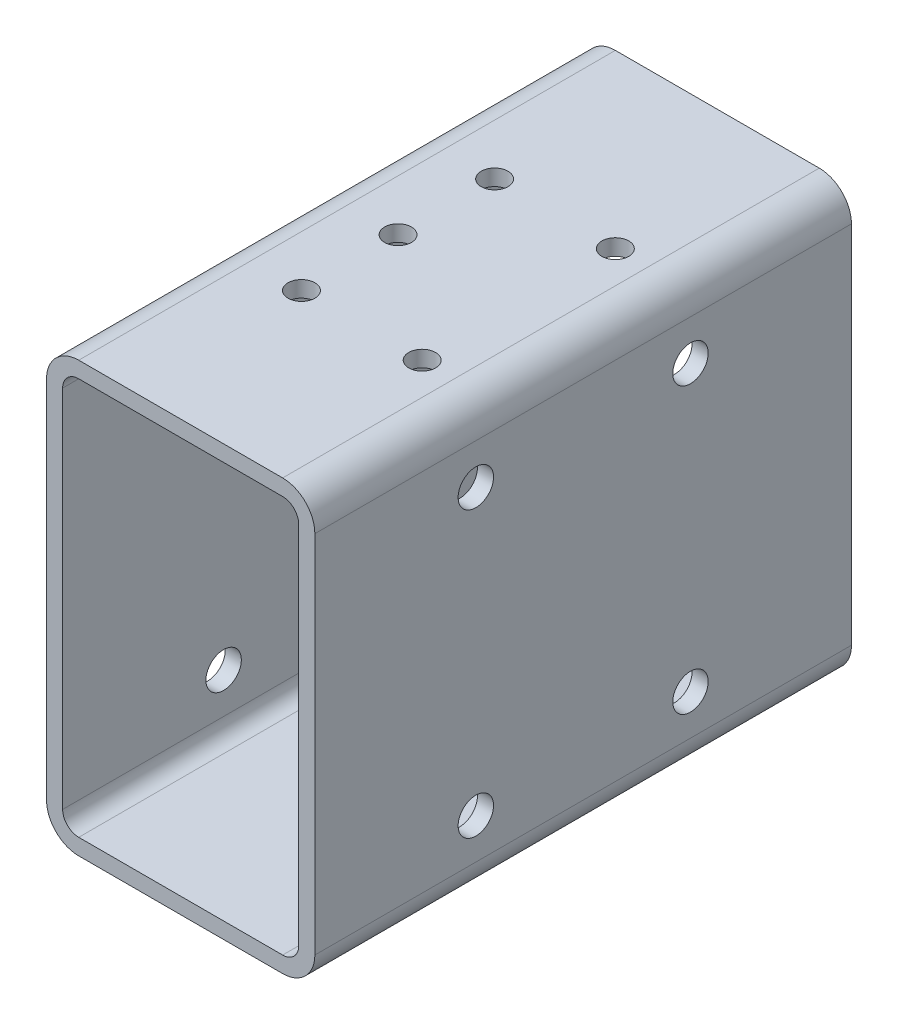
SolidWorks part; units mm, degrees
ref_plane "Front Plane" through (0, 0, 0) normal (0, 0, 1) x (1, 0, 0)
ref_plane "Top Plane" through (0, 0, 0) normal (0, 1, 0) x (1, 0, 0)
ref_plane "Right Plane" through (0, 0, 0) normal (1, 0, 0) x (0, 0, -1)
sketch "Sketch1" plane through (0, 0, 0) normal (0, 0, 1) x (1, 0, 0)
  line L0 (19, 37) -> (-19, 37)
  line L1 (19, -40) -> (-19, -40)
  line L2 (25, -34) -> (25, 34)
  line L3 (19, 40) -> (-19, 40)
  line L4 (-25, -34) -> (-25, 34)
  line L5 (25, -40) -> (-25, 40) construction
  line L6 (25, 40) -> (-25, -40) construction
  line L7 (-22, -34) -> (-22, 34)
  line L8 (19, -37) -> (-19, -37)
  line L9 (22, -34) -> (22, 34)
  arc A0 (-19, -40) -> (-25, -34) centre (-19, -34) cw
  arc A1 (19, -40) -> (25, -34) centre (19, -34) ccw
  arc A2 (25, 34) -> (19, 40) centre (19, 34) ccw
  arc A3 (-19, 40) -> (-25, 34) centre (-19, 34) ccw
  arc A4 (-19, 37) -> (-22, 34) centre (-19, 34) ccw
  arc A5 (-19, -37) -> (-22, -34) centre (-19, -34) cw
  arc A6 (19, -37) -> (22, -34) centre (19, -34) ccw
  arc A7 (22, 34) -> (19, 37) centre (19, 34) ccw
  point P0 (0, 0)
  dimension "D1" = 6
  dimension "D3" = 80
  dimension "D4" = 50
  dimension "D2" = 3
extrude "Boss-Extrude1" add sketch "Sketch1" along normal mid plane 100
sketch "Sketch2" plane through (25, 0, 0) normal (1, 0, 0) x (0, 0, -1)
  line L1 (20, 26.5) -> (-20, 26.5) construction
  line L2 (20, 26.5) -> (20, -26.5) construction
  line L3 (20, -26.5) -> (-20, -26.5) construction
  line L4 (-20, 26.5) -> (-20, -26.5) construction
  line L5 (20, 26.5) -> (-20, -26.5) construction
  line L6 (20, -26.5) -> (-20, 26.5) construction
  circle A0 centre (-20, 26.5) radius 3.3
  circle A1 centre (20, 26.5) radius 3.3
  circle A2 centre (20, -26.5) radius 3.3
  circle A3 centre (-20, -26.5) radius 3.3
  point P0 (0, 0)
  dimension "D3" = 6.6
  dimension "D1" = 53
  dimension "D2" = 40
extrude "Cut-Extrude1" cut sketch "Sketch2" against normal through all
sketch "Sketch3" plane through (0, 40, 0) normal (0, 1, 0) x (1, 0, 0)
  line L0 (-24.6642, 0) -> (5.453, 0) construction
  line L1 (-9.5, 18) -> (-9.5, -18) construction
  line L2 (-9.5, 18) -> (13, 18) construction
  line L3 (13, 18) -> (13, -18) construction
  line L4 (25, -50) -> (25, 50) construction
  circle A0 centre (-9.5, 18) radius 2.5
  circle A1 centre (-9.5, 0) radius 2.5
  circle A2 centre (-9.5, -18) radius 2.5
  circle A3 centre (13, 18) radius 2.5
  circle A4 centre (13, -18) radius 2.5
  point P5 (-9.5, 0)
  dimension "D2" = 5
  dimension "D1" = 36
  dimension "D3" = 22.5
  dimension "D4" = 12
extrude "Cut-Extrude2" cut sketch "Sketch3" against normal up to surface (3 mm away) up to face at (0, 37, 0)
equation "\"M5_tap\"=4.2mm"
equation "\"M5_clearence\"=5.5mm"
equation "\"M6_tap\"=5mm"
equation "\"M6_clearence\"=6.6mm"
equation "\"work_area_width\"=1100mm"
equation "\"work_area_depth\"=900mm"
equation "\"D3@Sketch1\"=\"steel_zbox_width\""
equation "\"D4@Sketch1\"=\"steel_zbox_height\""
equation "\"D1@Sketch1\"=\"steel_zbox_radius\""
equation "\"D2@Sketch1\"=\"steel_zbox_wall_thickness\""
equation "\"D1@Boss-Extrude1\"=\"length\""
equation "\"steel_base_width\"=80mm"
equation "\"steel_base_height\"=50mm"
equation "\"steel_base_wall_thickness\"=3mm"
equation "\"steel_base_radius\"=6mm"
equation "\"steel_sides_width\"=80mm"
equation "\"steel_sides_height\"=50mm"
equation "\"steel_sides_wall_thickness\"=5mm"
equation "\"steel_sides_radius\"=6mm"
equation "\"steel_gantry_width\"=80mm"
equation "\"steel_gantry_height\"=50mm"
equation "\"steel_gantry_wall_thickness\"=6mm"
equation "\"steel_gantry_radius\"=6mm"
equation "\"D3@Sketch2\"=\"M6_clearence\""
equation "\"D2@Sketch3\"=\"M6_tap\""
equation "\"steel_rollers_width\"=80mm"
equation "\"steel_rollers_height\"=50mm"
equation "\"steel_rollers_wall_thickness\"=6mm"
equation "\"steel_rollers_radius\"=6mm"
equation "\"steel_zbox_width\"=80mm"
equation "\"steel_zbox_height\"=50mm"
equation "\"steel_zbox_wall_thickness\"=3mm"
equation "\"steel_zbox_radius\"=6mm"
equation "\"D4@Sketch3\"=\"steel_zbox_radius\" * 2"
equation "\"length\"= 100mm"
